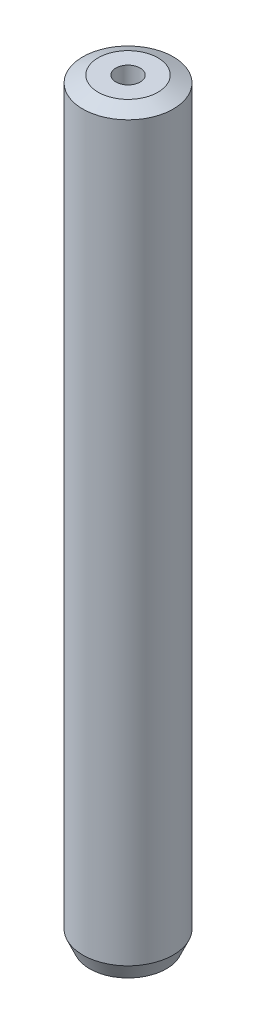
SolidWorks part; units mm, degrees
ref_plane "Front Plane" through (0, 0, 0) normal (0, 0, 1) x (1, 0, 0)
ref_plane "Top Plane" through (0, 0, 0) normal (0, 1, 0) x (1, 0, 0)
ref_plane "Right Plane" through (0, 0, 0) normal (1, 0, 0) x (0, 0, -1)
sketch "Sketch1" plane through (0, 0, 0) normal (0, 1, 0) x (1, 0, 0)
  circle A0 centre (0, 0) radius 10
  dimension "SHAFT_OD" = 20
extrude "Boss-Extrude1" add sketch "Sketch1" along normal blind 166.8206
sketch "Sketch2" plane through (0, 0, 0) normal (0, 1, 0) x (1, 0, 0)
  circle A0 centre (0, 0) radius 2.6863
  dimension "BORE_D" = 5.3725
extrude "Cut-Extrude1" cut sketch "Sketch2" along normal through all
chamfer "Chamfer1" distance 1.5091 angle 66.06 2 edges at (0, 166.8206, 10) (0, 0, 10) first distance on face at (0, 166.8206, 10) first distance on face at (0, 0, 2.6863)
